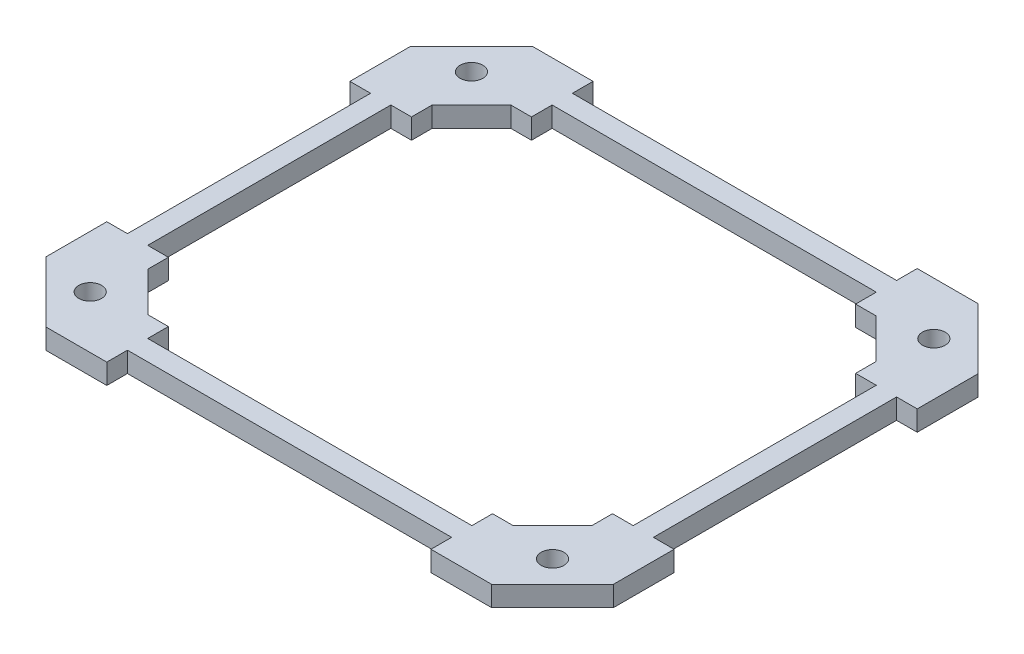
SolidWorks part; units mm, degrees
material "Rubber"
ref_plane "Front Plane" through (0, 0, 0) normal (0, 0, 1) x (1, 0, 0)
ref_plane "Top Plane" through (0, 0, 0) normal (0, 1, 0) x (1, 0, 0)
ref_plane "Right Plane" through (0, 0, 0) normal (1, 0, 0) x (0, 0, -1)
sketch "Sketch1" plane through (0, 0, 0) normal (0, 1, 0) x (1, 0, 0)
  line L0 (-57.15, -56.896) -> (-69.596, -44.45) construction
  line L1 (-69.596, -44.45) -> (-69.596, -38.1) construction
  line L2 (-69.596, -38.1) -> (-88.9, -38.1) construction
  line L3 (-88.9, -38.1) -> (-88.9, -57.15) construction
  line L4 (-88.9, -57.15) -> (-69.85, -76.2) construction
  line L5 (-69.85, -76.2) -> (-50.8, -76.2) construction
  line L6 (-50.8, -76.2) -> (-50.8, -56.896) construction
  line L7 (-50.8, -56.896) -> (-57.15, -56.896) construction
  line L9 (-82.423, 38.1) -> (-82.423, -38.1) construction
  line L11 (-76.073, -38.1) -> (-76.073, 38.1) construction
  line L13 (50.8, -63.373) -> (-50.8, -63.373) construction
  line L15 (-50.8, -69.723) -> (50.8, -69.723) construction
  line L16 (69.596, -44.45) -> (57.15, -56.896) construction
  line L17 (57.15, -56.896) -> (50.8, -56.896) construction
  line L18 (50.8, -56.896) -> (50.8, -76.2) construction
  line L19 (50.8, -76.2) -> (69.85, -76.2) construction
  line L20 (69.85, -76.2) -> (88.9, -57.15) construction
  line L21 (88.9, -57.15) -> (88.9, -38.1) construction
  line L22 (88.9, -38.1) -> (69.596, -38.1) construction
  line L23 (69.596, -38.1) -> (69.596, -44.45) construction
  line L25 (76.073, 38.1) -> (76.073, -38.1) construction
  line L27 (82.423, -38.1) -> (82.423, 38.1) construction
  line L29 (-50.8, 63.373) -> (50.8, 63.373) construction
  line L31 (50.8, 69.723) -> (-50.8, 69.723) construction
  line L32 (57.15, 56.896) -> (69.596, 44.45) construction
  line L33 (69.596, 44.45) -> (69.596, 38.1) construction
  line L34 (69.596, 38.1) -> (88.9, 38.1) construction
  line L35 (88.9, 38.1) -> (88.9, 57.15) construction
  line L36 (88.9, 57.15) -> (69.85, 76.2) construction
  line L37 (69.85, 76.2) -> (50.8, 76.2) construction
  line L38 (50.8, 76.2) -> (50.8, 56.896) construction
  line L39 (50.8, 56.896) -> (57.15, 56.896) construction
  line L40 (-69.596, 44.45) -> (-57.15, 56.896) construction
  line L41 (-57.15, 56.896) -> (-50.8, 56.896) construction
  line L42 (-50.8, 56.896) -> (-50.8, 76.2) construction
  line L43 (-50.8, 76.2) -> (-69.85, 76.2) construction
  line L44 (-69.85, 76.2) -> (-88.9, 57.15) construction
  line L45 (-88.9, 57.15) -> (-88.9, 38.1) construction
  line L46 (-88.9, 38.1) -> (-69.596, 38.1) construction
  line L47 (-69.596, 38.1) -> (-69.596, 44.45) construction
  line L48 (-57.15, -56.896) -> (-69.596, -44.45)
  line L49 (-69.596, -44.45) -> (-69.596, -38.1)
  line L50 (-69.596, -38.1) -> (-76.073, -38.1)
  line L51 (-88.9, -38.1) -> (-88.9, -57.15)
  line L52 (-88.9, -57.15) -> (-69.85, -76.2)
  line L53 (-69.85, -76.2) -> (-50.8, -76.2)
  line L54 (-50.8, -76.2) -> (-50.8, -69.723)
  line L55 (-50.8, -56.896) -> (-57.15, -56.896)
  line L57 (-82.423, 38.1) -> (-82.423, -38.1)
  line L59 (-76.073, -38.1) -> (-76.073, 38.1)
  line L61 (50.8, -63.373) -> (-50.8, -63.373)
  line L63 (-50.8, -69.723) -> (50.8, -69.723)
  line L64 (69.596, -44.45) -> (57.15, -56.896)
  line L65 (57.15, -56.896) -> (50.8, -56.896)
  line L66 (50.8, -56.896) -> (50.8, -63.373)
  line L67 (50.8, -76.2) -> (69.85, -76.2)
  line L68 (69.85, -76.2) -> (88.9, -57.15)
  line L69 (88.9, -57.15) -> (88.9, -38.1)
  line L70 (88.9, -38.1) -> (82.423, -38.1)
  line L71 (69.596, -38.1) -> (69.596, -44.45)
  line L73 (76.073, 38.1) -> (76.073, -38.1)
  line L75 (82.423, -38.1) -> (82.423, 38.1)
  line L77 (-50.8, 63.373) -> (50.8, 63.373)
  line L79 (50.8, 69.723) -> (-50.8, 69.723)
  line L80 (57.15, 56.896) -> (69.596, 44.45)
  line L81 (69.596, 44.45) -> (69.596, 38.1)
  line L82 (69.596, 38.1) -> (76.073, 38.1)
  line L83 (88.9, 38.1) -> (88.9, 57.15)
  line L84 (88.9, 57.15) -> (69.85, 76.2)
  line L85 (69.85, 76.2) -> (50.8, 76.2)
  line L86 (50.8, 76.2) -> (50.8, 69.723)
  line L87 (50.8, 56.896) -> (57.15, 56.896)
  line L88 (-69.596, 44.45) -> (-57.15, 56.896)
  line L89 (-57.15, 56.896) -> (-50.8, 56.896)
  line L90 (-50.8, 56.896) -> (-50.8, 63.373)
  line L91 (-50.8, 76.2) -> (-69.85, 76.2)
  line L92 (-69.85, 76.2) -> (-88.9, 57.15)
  line L93 (-88.9, 57.15) -> (-88.9, 38.1)
  line L94 (-88.9, 38.1) -> (-82.423, 38.1)
  line L95 (-69.596, 38.1) -> (-69.596, 44.45)
  line L96 (50.8, 63.373) -> (50.8, 56.896)
  line L97 (82.423, 38.1) -> (88.9, 38.1)
  line L98 (76.073, -38.1) -> (69.596, -38.1)
  line L99 (50.8, -69.723) -> (50.8, -76.2)
  line L100 (-50.8, 69.723) -> (-50.8, 76.2)
  line L101 (-76.073, 38.1) -> (-69.596, 38.1)
  line L102 (-82.423, -38.1) -> (-88.9, -38.1)
  line L103 (-50.8, -63.373) -> (-50.8, -56.896)
extrude "Boss-Extrude1" add sketch "Sketch1" along normal blind 6.35
hole_wizard "1/4 Clearance Hole1" positions "Sketch2" profile "Sketch3" hole size "1/4" standard "ANSI Inch" end condition through all
sketch "Sketch2" plane through (0, 0, 0) normal (0, -1, 0) x (-1, 0, 0)
  point P0 (-72.4527, 59.7527)
  point P3 (72.4527, 59.7527)
  point P6 (72.4527, -59.7527)
  point P9 (-72.4527, -59.7527)
sketch "Sketch3" plane through (72.4527, 0, -59.7527) normal (1, 0, 0) x (0, 0, -1)
  line L0 (0, 0) -> (0, 6.35)
  line L1 (0, 6.35) -> (3.5712, 6.35)
  line L2 (3.5712, 6.35) -> (3.5712, 0)
  line L5 (3.5712, 0) -> (0, 0)
  line L11 (0, -6.35) -> (0, 107.95) construction
  dimension "Thru Hole Dia." = 7.1425
  dimension "Thru Hole Depth" = 6.35
